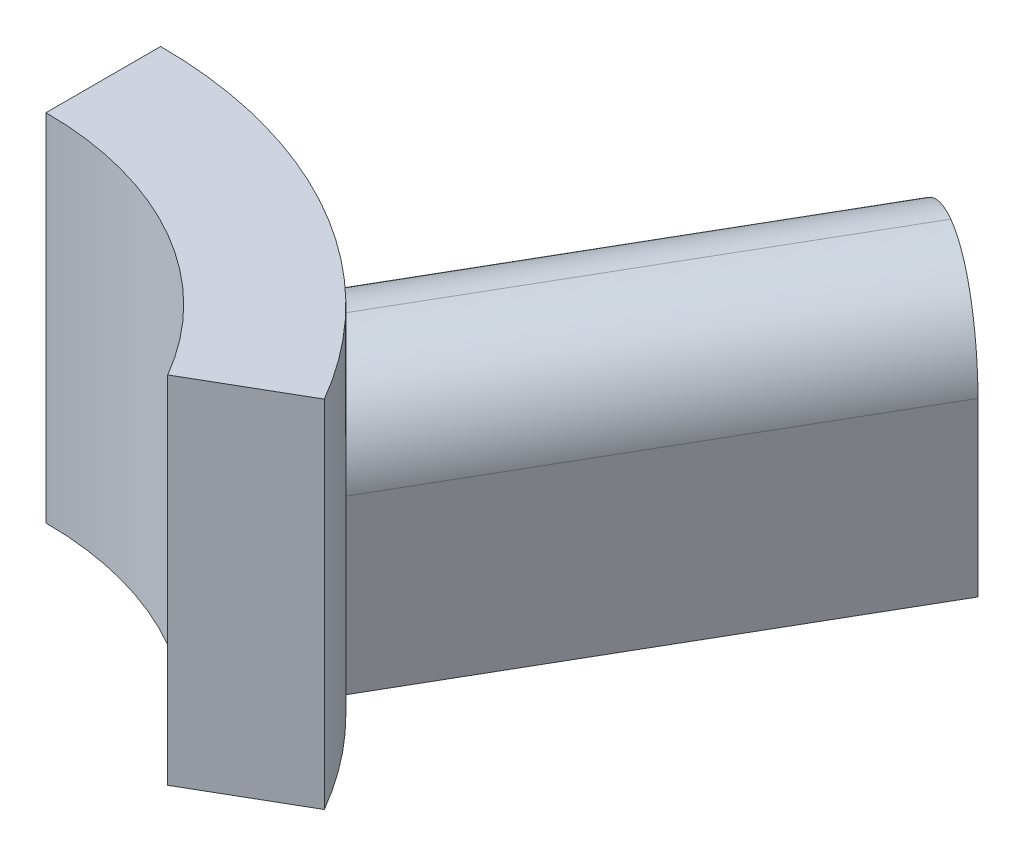
SolidWorks part; units mm, degrees
ref_plane "Front Plane" through (0, 0, 0) normal (0, 0, 1) x (1, 0, 0)
ref_plane "Top Plane" through (0, 0, 0) normal (0, 1, 0) x (1, 0, 0)
ref_plane "Right Plane" through (0, 0, 0) normal (1, 0, 0) x (0, 0, -1)
sketch "Sketch3" plane through (0, 0, 0) normal (0, 1, 0) x (1, 0, 0)
  line L0 (0, 14.5) -> (0, 19.5)
  line L1 (12.5574, 7.25) -> (16.8875, 9.75)
  line L2 (0, 0) -> (23.7984, 41.22) construction
  arc A0 (12.5574, 7.25) -> (0, 14.5) centre (0, 0) ccw
  arc A1 (0, 19.5) -> (16.8875, 9.75) centre (0, 0) cw
  dimension "D1" = 14.5
  dimension "D4" = 19.5
  dimension "D2" = 60
  dimension "D3" = 60
  dimension "D5" = 5
  dimension "D6" = 30
extrude "Boss-Extrude1" add sketch "Sketch3" along normal blind 15.5
sketch "Sketch5" plane through (0, 0, 0) normal (0, -1, 0) x (1, 0, 0)
  line L0 (6.0786, -18.5284) -> (16.1844, -36.0322)
  line L1 (0, 0) -> (19.0643, -33.0203) construction
  line L2 (0, -19.5) -> (0, -14.5) construction
  line L3 (13.0068, -14.5284) -> (23.1126, -32.0322)
  line L7 (0, -14.5) -> (0, -19.5)
  line L8 (16.8875, -9.75) -> (12.5574, -7.25)
  arc A0 (0, -19.5) -> (16.8875, -9.75) centre (0, 0) ccw construction
  arc A2 (23.1126, -32.0322) -> (16.1844, -36.0322) centre (0, 0) cw
  arc A3 (0, -14.5) -> (12.5574, -7.25) centre (0, 0) ccw
  arc A4 (0, -19.5) -> (16.8875, -9.75) centre (0, 0) ccw
  arc A6 (6.0786, -18.5284) -> (13.0068, -14.5284) centre (0, 0) ccw
  point P22 (19.75, -34.208)
  dimension "D7" = 19.5
  dimension "D8" = 39.5
  dimension "D9" = 20.2116
  dimension "D1" = 30
  dimension "D2" = 20
  dimension "D3" = 4
  dimension "D5" = 4
  dimension "D10" = 20.2116
  dimension "D6" = 0
extrude "Boss-Extrude2" add sketch "Sketch5" against normal blind 11.5
ref_plane "Plane1" through (6.0786, 11.5, -18.5284) normal (0.5, 0, -0.866) x (-0.866, 0, -0.5)
fillet "Fillet1" radius 4 2 edges at (18.0597, 11.5, -23.2803) (11.1315, 11.5, -27.2803)
